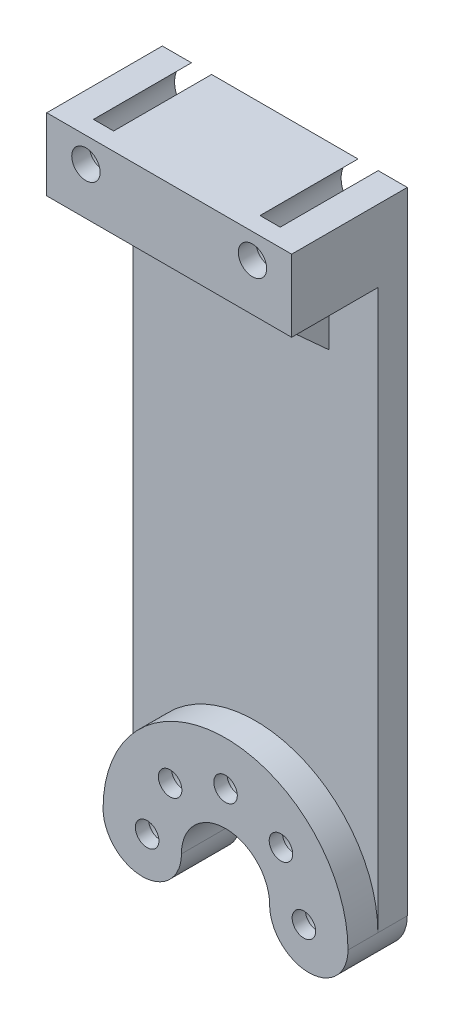
SolidWorks part; units mm, degrees
ref_plane "Plano frontal" through (0, 0, 0) normal (0, 0, 1) x (1, 0, 0)
ref_plane "Plano superior" through (0, 0, 0) normal (0, 1, 0) x (1, 0, 0)
ref_plane "Plano direito" through (0, 0, 0) normal (1, 0, 0) x (0, 0, -1)
sketch "Esboço1" plane through (0, 0, 0) normal (0, 0, 1) x (1, 0, 0)
  arc A0 (4.5, 0) -> (-4.5, 0) centre (0, 0) ccw
  arc A1 (12.5, 0) -> (-12.5, 0) centre (0, 0) ccw
  arc A2 (12.5, 0) -> (4.5, 0) centre (8.5, 0) cw
  arc A3 (-4.5, 0) -> (-12.5, 0) centre (-8.5, 0) cw
  arc A4 (4, 0) -> (-4, 0) centre (0, 0) ccw construction
  circle A6 centre (8.5, 61.8383) radius 1.35 construction
  point P13 (0, 0)
  dimension "D1" = 0.5
  dimension "D2" = 4
extrude "Ressalto-extrusão1" add sketch "Esboço1" against normal offset from surface (3.05 mm away) 2 offset beyond the face yes
sketch "Esboço2" plane through (0, 0, -3.05) normal (0, 0, -1) x (-1, 0, 0)
  line L1 (-12.5, 64.3883) -> (12.5, 64.3883)
  line L3 (9.2, 64.6383) -> (-9.2, 64.6383) construction
  line L6 (-12.5, 64.3883) -> (-12.5, 0)
  line L9 (12.5, 64.3883) -> (12.5, 0)
  arc A6 (4.5, 0) -> (12.5, 0) centre (8.5, 0) ccw construction
  arc A7 (-12.5, 0) -> (-4.5, 0) centre (-8.5, 0) ccw construction
  arc A8 (4.5, 0) -> (12.5, 0) centre (8.5, 0) ccw
  arc A9 (-12.5, 0) -> (-4.5, 0) centre (-8.5, 0) ccw
  arc A13 (4.5, 0) -> (-4.5, 0) centre (0, 0) ccw construction
  arc A16 (4.5, 0) -> (-4.5, 0) centre (0, 0) ccw
  dimension "D3" = 0.25
extrude "Ressalto-extrusão2" add sketch "Esboço2" along normal blind 3
sketch "Esboço4" plane through (0, 0, -6.05) normal (0, 0, -1) x (-1, 0, 0)
  line L1 (-12.5, 64.3883) -> (12.5, 64.3883)
  line L2 (-12.5, 64.3883) -> (-12.5, 57.0383)
  line L3 (-12.5, 57.0383) -> (12.5, 57.0383)
  line L4 (12.5, 64.3883) -> (12.5, 57.0383)
  line L5 (12.5, 0) -> (12.5, 64.3883) construction
  line L6 (-12.7, 59.0383) -> (12.7, 59.0383) construction
  dimension "D1" = 2
extrude "Ressalto-extrusão3" add sketch "Esboço4" against normal up to surface (11.8 mm away)
hole_wizard "Rebaixo para SHCS M2.51" positions "Sketch1" profile "Sketch2" counterbore size "M2.5" standard "Ansi Metric" end condition up to next
sketch "Sketch1" plane through (0, 0, -6.05) normal (0, 0, -1) x (-1, 0, 0)
  circle A0 centre (-8.5, 61.8383) radius 1.35 construction
  circle A1 centre (8.5, 61.8383) radius 1.35 construction
  point P0 (-8.5, 61.8383)
  point P3 (8.5, 61.8383)
sketch "Sketch2" plane through (8.5, 61.8383, -6.05) normal (1, 0, 0) x (0, 1, 0)
  line L0 (0, 0) -> (0, 11.8)
  line L1 (0, 11.8) -> (1.45, 11.8)
  line L3 (1.45, 11.8) -> (1.45, 10)
  line L4 (1.45, 10) -> (2.75, 10)
  line L5 (2.75, 10) -> (2.75, 0)
  line L7 (2.75, 0) -> (0, 0)
  line L11 (0, -6.35) -> (0, 107.95) construction
  dimension "Thru Hole Dia." = 2.9
  dimension "Thru Hole Depth" = 11.8
  dimension "C'Bore Dia." = 5.5
  dimension "C'Bore Depth" = 10
hole_wizard "Rebaixo para SHCS M21" positions "Sketch3" profile "Sketch4" counterbore size "M2" standard "Ansi Metric" end condition up to next
sketch "Sketch3" plane through (0, 0, -6.05) normal (0, 0, -1) x (-1, 0, 0)
  line L0 (0, 0) -> (-8, 0) construction
  line L1 (0, 0) -> (-5.6569, 5.6569) construction
  line L2 (0, 0) -> (0, 8) construction
  line L3 (0, 0) -> (5.6569, 5.6569) construction
  line L4 (0, 0) -> (8, 0) construction
  arc A0 (-8.8, 0) -> (-7.2, 0) centre (-8, 0) ccw construction
  point P0 (-8, 0)
  point P15 (-5.6569, 5.6569)
  point P17 (0, 8)
  point P19 (5.6569, 5.6569)
  point P21 (8, 0)
  dimension "D1" = 5
sketch "Sketch4" plane through (8, 0, -6.05) normal (1, 0, 0) x (0, 1, 0)
  line L0 (0, 0) -> (0, 6.05)
  line L1 (0, 6.05) -> (1.2, 6.05)
  line L3 (1.2, 6.05) -> (1.2, 4.7)
  line L4 (1.2, 4.7) -> (2.2, 4.7)
  line L5 (2.2, 4.7) -> (2.2, 0)
  line L7 (2.2, 0) -> (0, 0)
  line L11 (0, -6.35) -> (0, 107.95) construction
  dimension "Thru Hole Dia." = 2.4
  dimension "Thru Hole Depth" = 6.05
  dimension "C'Bore Dia." = 4.4
  dimension "C'Bore Depth" = 4.7
sketch "Esboço5" plane through (0, 0, 0) normal (1, 0, 0) x (0, 0, -1)
  line L0 (-5.75, 57.0383) -> (3.05, 49.0383)
  line L1 (3.05, 57.0383) -> (3.05, 0) construction
  line L2 (-5.75, 57.0383) -> (3.05, 57.0383) construction
  dimension "D1" = 8
rib "Nervura1" sketch "Esboço5" sketch "Esboço5" thickness 15 extrusion direction parallel to sketch draft on no parameters "D1"=15
sketch "Esboço6" plane through (0, 0, -3.05) normal (0, 0, 1) x (1, 0, 0)
  line L0 (7.5, 49.0383) -> (-7.5, 49.0383) construction
  line L1 (4.4016, 49.0383) -> (-4.5372, 49.0383)
  line L2 (4.4016, 49.0383) -> (4.4016, 57.0383)
  line L3 (4.4016, 57.0383) -> (-4.5372, 57.0383)
  line L4 (-4.5372, 49.0383) -> (-4.5372, 57.0383)
  line L5 (4.4251, 52.1001) -> (4.4021, 49.1002) construction
  line L6 (-7.5, 57.0383) -> (7.5, 57.0383) construction
  line L7 (-4.5976, 49.1693) -> (-4.5746, 52.1692) construction
extrude "Corte-extrusão1" cut sketch "Esboço6" along normal up to next
